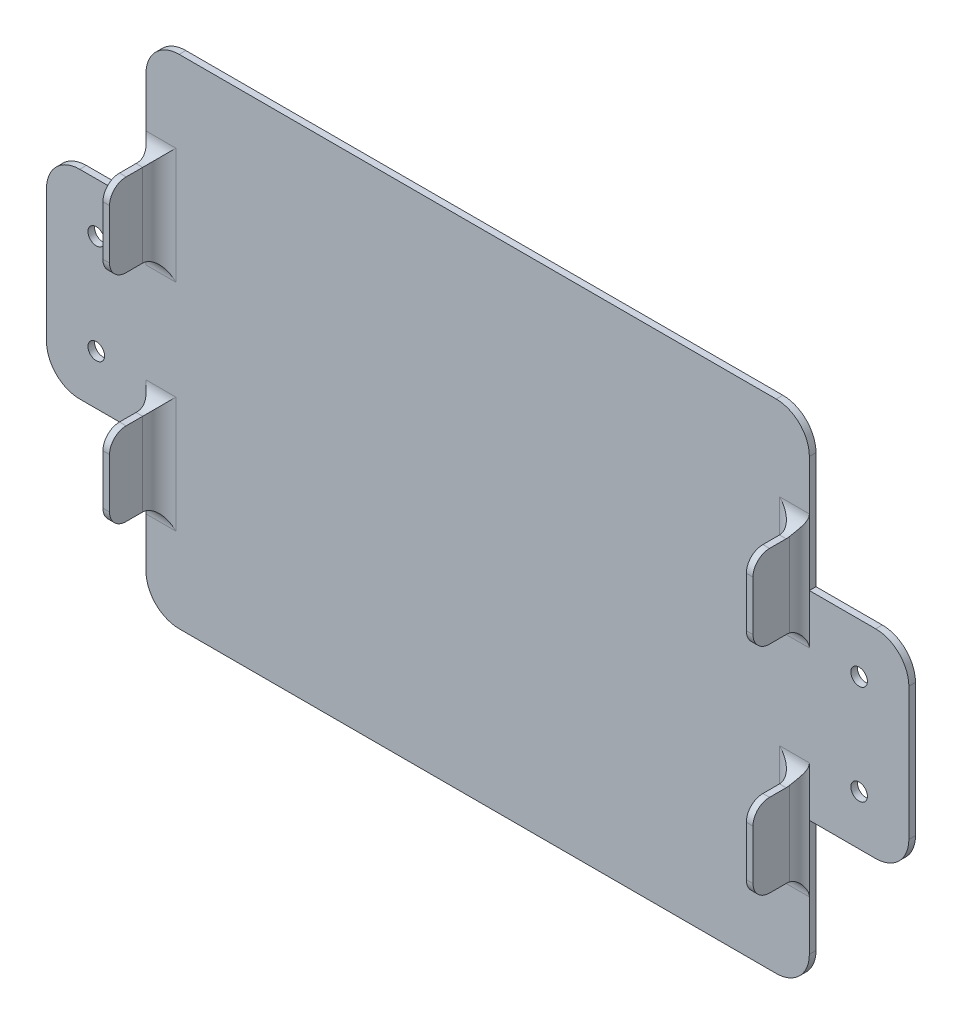
SolidWorks part; units mm, degrees
ref_plane "Plan de face" through (0, 0, 0) normal (0, 0, 1) x (1, 0, 0)
ref_plane "Plan de dessus" through (0, 0, 0) normal (0, 1, 0) x (1, 0, 0)
ref_plane "Plan de droite" through (0, 0, 0) normal (1, 0, 0) x (0, 0, -1)
sketch "Esquisse1" plane through (0, 0, 0) normal (0, 0, 1) x (1, 0, 0)
  line L1 (0, 0) -> (200, 0)
  line L2 (0, 0) -> (0, 150)
  line L3 (0, 150) -> (200, 150)
  line L4 (200, 0) -> (200, 150)
  line L5 (0, 0) -> (200, 150) construction
  line L6 (0, 150) -> (200, 0) construction
  point P4 (100, 75)
  dimension "D1" = 150
  dimension "D2" = 200
extrude "Boss.-Extru.1" add sketch "Esquisse1" along normal blind 2
fillet "Congé1" radius 10 4 edges at (200, 0, 1) (0, 0, 1) (0, 150, 1) (200, 150, 1)
sketch "Esquisse2" plane through (0, 0, 2) normal (0, 0, 1) x (1, 0, 0)
  line L0 (0, 75) -> (40.344, 75) construction
  line L1 (2, 120) -> (4, 120)
  line L2 (2, 120) -> (2, 95)
  line L3 (2, 95) -> (4, 95)
  line L4 (4, 120) -> (4, 95)
  line L5 (2, 120) -> (4, 95) construction
  line L6 (2, 95) -> (4, 120) construction
  line L7 (0, 140) -> (0, 10) construction
  line L8 (100, 150) -> (100, 130.2198) construction
  line L9 (190, 150) -> (10, 150) construction
  line L10 (2, 55) -> (4, 55)
  line L11 (4, 30) -> (4, 55)
  line L12 (2, 30) -> (4, 30)
  line L13 (2, 30) -> (2, 55)
  line L14 (198, 95) -> (196, 120) construction
  line L15 (198, 120) -> (196, 95) construction
  line L16 (198, 30) -> (198, 55)
  line L17 (198, 30) -> (196, 30)
  line L18 (196, 30) -> (196, 55)
  line L19 (198, 55) -> (196, 55)
  line L20 (196, 120) -> (196, 95)
  line L21 (198, 95) -> (196, 95)
  line L22 (198, 120) -> (198, 95)
  line L23 (198, 120) -> (196, 120)
  point P4 (3, 107.5)
  point P25 (197, 107.5)
  dimension "D1" = 2
  dimension "D2" = 2
  dimension "D3" = 25
  dimension "D4" = 20
extrude "Boss.-Extru.2" add sketch "Esquisse2" along normal blind 15
fillet "Congé2" radius 5 24 edges at (197, 120, 17) (197, 120, 2) (197, 95, 17) (197, 55, 2) (197, 55, 17) (198, 107.5, 2) (196, 107.5, 2) (197, 95, 2) (196, 42.5, 2) (197, 30, 17) (198, 42.5, 2) (197, 30, 2) (3, 30, 2) (4, 42.5, 2) (3, 55, 2) (2, 42.5, 2) (3, 120, 2) (3, 95, 2) (4, 107.5, 2) (2, 107.5, 2) (3, 30, 17) (3, 55, 17) (3, 120, 17) (3, 95, 17)
sketch "Esquisse3" plane through (0, 0, 2) normal (0, 0, 1) x (1, 0, 0)
  line L0 (0, 60) -> (9, 60) construction
  line L1 (0, 90) -> (4.5, 90)
  line L2 (0, 90) -> (0, 60)
  line L3 (0, 60) -> (4.5, 60)
  line L4 (4.5, 90) -> (4.5, 60)
  line L5 (0, 90) -> (4.5, 60) construction
  line L6 (0, 60) -> (4.5, 90) construction
  line L7 (200, 90) -> (191, 90) construction
  line L8 (195.5, 90) -> (200, 90)
  line L9 (195.5, 90) -> (195.5, 60)
  line L10 (195.5, 60) -> (200, 60)
  line L11 (200, 90) -> (200, 60)
  line L12 (195.5, 90) -> (200, 60) construction
  line L13 (195.5, 60) -> (200, 90) construction
  point P4 (2.25, 75)
  point P12 (197.75, 75)
extrude "Enlèv. mat.-Extru.1" cut sketch "Esquisse3" against normal blind 15
sketch "Esquisse4" plane through (0, 0, 0) normal (0, 0, -1) x (-1, 0, 0)
  line L0 (0, 60) -> (0, 10) construction
  line L1 (-20, 105) -> (20, 105)
  line L2 (-20, 105) -> (-20, 45)
  line L3 (-20, 45) -> (20, 45)
  line L4 (30, 95) -> (30, 55)
  line L5 (-20, 105) -> (30, 45) construction
  line L6 (-20, 45) -> (30, 105) construction
  line L7 (-4.5, 90) -> (-4.5, 60) construction
  line L8 (-100, 150) -> (-100, 112.1192) construction
  line L9 (-190, 150) -> (-10, 150) construction
  line L10 (-180, 45) -> (-220, 45)
  line L11 (-230, 95) -> (-230, 55)
  line L12 (-180, 105) -> (-220, 105)
  line L13 (-180, 105) -> (-180, 45)
  arc A0 (20, 105) -> (30, 95) centre (20, 95) cw
  arc A1 (20, 45) -> (30, 55) centre (20, 55) ccw
  arc A2 (-220, 45) -> (-230, 55) centre (-220, 55) cw
  arc A3 (-220, 105) -> (-230, 95) centre (-220, 95) ccw
  circle A4 centre (15, 90) radius 2.5
  circle A5 centre (15, 60) radius 2.5
  circle A6 centre (-215, 60) radius 2.5
  circle A7 centre (-215, 90) radius 2.5
  point P4 (5, 75)
  point P11 (-4.5, 75)
  point P33 (0, 0)
  dimension "D4" = 10
  dimension "D5" = 5
  dimension "D1" = 20
  dimension "D2" = 50
  dimension "D3" = 60
  dimension "D6" = 15
  dimension "D7" = 15
  dimension "D8" = 15
extrude "Boss.-Extru.3" add sketch "Esquisse4" against normal blind 2
